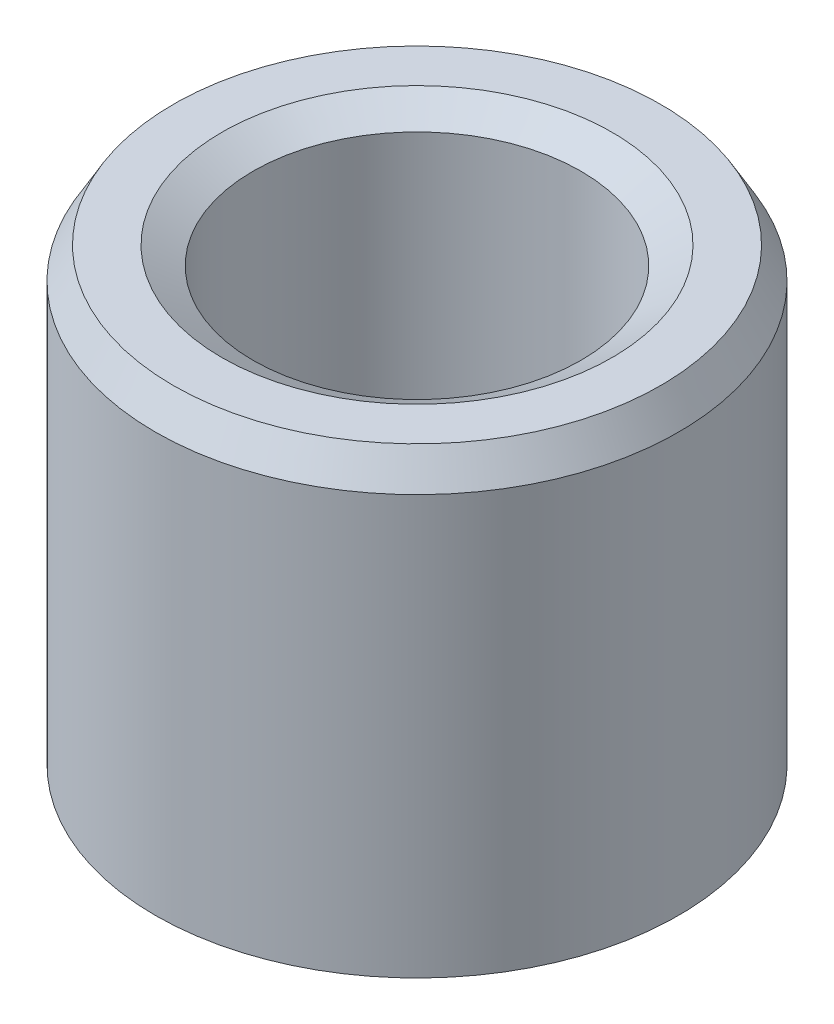
SolidWorks part; units mm, degrees
ref_plane "Front Plane" through (0, 0, 0) normal (0, 0, 1) x (1, 0, 0)
ref_plane "Top Plane" through (0, 0, 0) normal (0, 1, 0) x (1, 0, 0)
ref_plane "Right Plane" through (0, 0, 0) normal (1, 0, 0) x (0, 0, -1)
sketch "Sketch1" plane through (0, 0, 0) normal (0, 1, 0) x (1, 0, 0)
  circle A0 centre (0, 0) radius 7.5
  dimension "SLEEVE_OD" = 15
extrude "Boss-Extrude1" add sketch "Sketch1" along normal blind 13.4106
sketch "Sketch2" plane through (0, 0, 0) normal (0, 1, 0) x (1, 0, 0)
  circle A0 centre (0, 0) radius 4.6982
  dimension "BORE_D" = 9.3964
extrude "Cut-Extrude1" cut sketch "Sketch2" along normal through all
chamfer "Chamfer1" distance 0.8956 angle 30 4 edges at (0, 13.4106, 4.6982) (0, 0, 4.6982) (0, 0, 7.5) (0, 13.4106, 7.5) first distance on face at (0, 13.4106, 4.6982) first distance on face at (0, 0, 4.6982) first distance on face at (0, 13.4106, 7.5)
